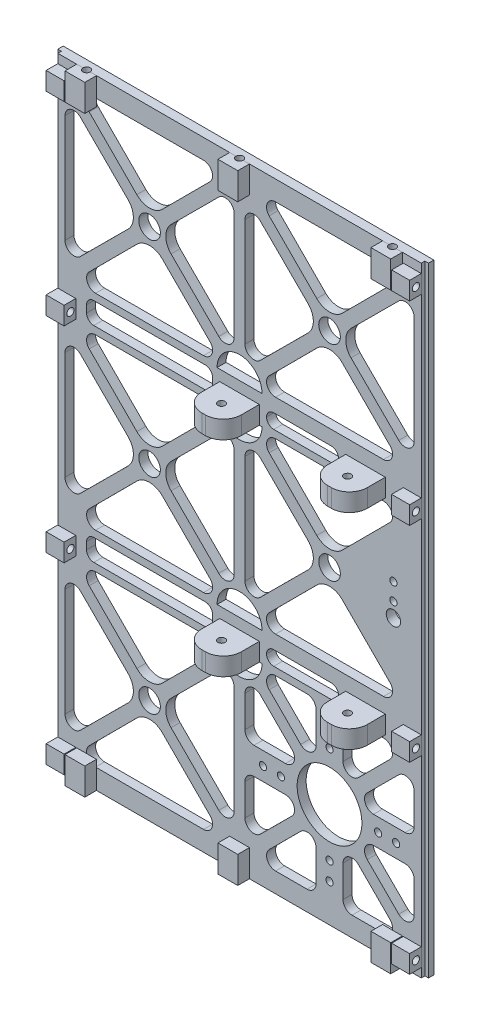
SolidWorks part; units mm, degrees
ref_plane "Přední rovina" through (0, 0, 0) normal (0, 0, 1) x (1, 0, 0)
ref_plane "Horní rovina" through (0, 0, 0) normal (0, 1, 0) x (1, 0, 0)
ref_plane "Pravá rovina" through (0, 0, 0) normal (1, 0, 0) x (0, 0, -1)
sketch "Skica1" plane through (0, 0, 0) normal (0, 0, 1) x (1, 0, 0)
  line L0 (0, 0) -> (0, 172) construction
  line L1 (-103, 172) -> (103, 172)
  line L2 (103, 172) -> (103, -172)
  line L3 (0, 0) -> (103, 0) construction
  line L4 (-103, 172) -> (-103, -172)
  line L5 (-103, -172) -> (103, -172)
  point P9 (-103, 0)
  dimension "D1" = 344
  dimension "D2" = 206
extrude "Přidat vysunutím1" add sketch "Skica1" along normal blind 5
sketch "Skica3" plane through (0, 0, 5) normal (0, 0, 1) x (1, 0, 0)
  line L0 (0, 0) -> (50, 0) construction
  line L1 (0, 0) -> (0, 172) construction
  line L2 (103, 172) -> (-103, 172) construction
  line L3 (50, 0) -> (50, 42) construction
  line L4 (50, 42) -> (80, 42) construction
  line L5 (50, 0) -> (0, 50) construction
  line L6 (11.5308, 33.5403) -> (38.0616, 7.0805)
  line L7 (83.5403, 38.4692) -> (57.0805, 11.9384)
  line L8 (16.4597, 38.4692) -> (42.9195, 11.9384)
  line L9 (20, 47) -> (80, 47)
  line L10 (3, 30) -> (3, -30)
  line L11 (11.5308, -33.5403) -> (38.0616, -7.0805)
  line L12 (16.4597, -38.4692) -> (42.9195, -11.9384)
  line L13 (20, -47) -> (80, -47)
  line L14 (83.5403, -38.4692) -> (57.0805, -11.9384)
  line L15 (97, 30) -> (97, -30)
  line L16 (88.4692, -33.5403) -> (61.9384, -7.0805)
  line L17 (88.4692, 33.5403) -> (61.9384, 7.0805)
  line L18 (0, 57) -> (103, 57) construction
  line L19 (103, -172) -> (103, 172) construction
  line L20 (0, -57) -> (103, -57) construction
  line L21 (16.4597, -152.4692) -> (42.9195, -125.9384)
  line L22 (20, -161) -> (80, -161)
  line L23 (83.5403, -152.4692) -> (57.0805, -125.9384)
  line L24 (88.4692, -147.5403) -> (61.9384, -121.0805)
  line L25 (88.4692, -80.4597) -> (61.9384, -106.9195)
  line L26 (97, -144) -> (97, -84)
  line L27 (20, -67) -> (80, -67)
  line L28 (83.5403, -75.5308) -> (57.0805, -102.0616)
  line L29 (16.4597, -75.5308) -> (42.9195, -102.0616)
  line L30 (3, -144) -> (3, -84)
  line L31 (11.5308, -80.4597) -> (38.0616, -106.9195)
  line L32 (11.5308, -147.5403) -> (38.0616, -121.0805)
  line L34 (20, 161) -> (80, 161)
  line L35 (83.5403, 152.4692) -> (57.0805, 125.9384)
  line L36 (16.4597, 152.4692) -> (42.9195, 125.9384)
  line L37 (3, 84) -> (3, 144)
  line L38 (11.5308, 147.5403) -> (38.0616, 121.0805)
  line L39 (11.5308, 80.4597) -> (38.0616, 106.9195)
  line L40 (16.4597, 75.5308) -> (42.9195, 102.0616)
  line L41 (20, 67) -> (80, 67)
  line L42 (83.5403, 75.5308) -> (57.0805, 102.0616)
  line L43 (88.4692, 80.4597) -> (61.9384, 106.9195)
  line L44 (88.4692, 147.5403) -> (61.9384, 121.0805)
  line L45 (97, 84) -> (97, 144)
  line L46 (-20, -161) -> (-80, -161)
  line L47 (-83.5403, -152.4692) -> (-57.0805, -125.9384)
  line L48 (-16.4597, -152.4692) -> (-42.9195, -125.9384)
  line L49 (-97, -144) -> (-97, -84)
  line L50 (-88.4692, -80.4597) -> (-61.9384, -106.9195)
  line L51 (-88.4692, -147.5403) -> (-61.9384, -121.0805)
  line L52 (-16.4597, -75.5308) -> (-42.9195, -102.0616)
  line L53 (-83.5403, -75.5308) -> (-57.0805, -102.0616)
  line L54 (-20, -67) -> (-80, -67)
  line L55 (-11.5308, -147.5403) -> (-38.0616, -121.0805)
  line L56 (-11.5308, -80.4597) -> (-38.0616, -106.9195)
  line L57 (-3, -144) -> (-3, -84)
  line L58 (-20, -47) -> (-80, -47)
  line L59 (-83.5403, -38.4692) -> (-57.0805, -11.9384)
  line L60 (-16.4597, -38.4692) -> (-42.9195, -11.9384)
  line L61 (-88.4692, 33.5403) -> (-61.9384, 7.0805)
  line L62 (-88.4692, -33.5403) -> (-61.9384, -7.0805)
  line L63 (-97, 30) -> (-97, -30)
  line L64 (-3, 30) -> (-3, -30)
  line L65 (-11.5308, -33.5403) -> (-38.0616, -7.0805)
  line L66 (-11.5308, 33.5403) -> (-38.0616, 7.0805)
  line L67 (-16.4597, 38.4692) -> (-42.9195, 11.9384)
  line L68 (-20, 47) -> (-80, 47)
  line L69 (-83.5403, 38.4692) -> (-57.0805, 11.9384)
  line L70 (-20, 67) -> (-80, 67)
  line L71 (-83.5403, 75.5308) -> (-57.0805, 102.0616)
  line L72 (-16.4597, 75.5308) -> (-42.9195, 102.0616)
  line L73 (-97, 84) -> (-97, 144)
  line L74 (-88.4692, 147.5403) -> (-61.9384, 121.0805)
  line L75 (-88.4692, 80.4597) -> (-61.9384, 106.9195)
  line L76 (-16.4597, 152.4692) -> (-42.9195, 125.9384)
  line L77 (-83.5403, 152.4692) -> (-57.0805, 125.9384)
  line L78 (-20, 161) -> (-80, 161)
  line L79 (-11.5308, 80.4597) -> (-38.0616, 106.9195)
  line L80 (-11.5308, 147.5403) -> (-38.0616, 121.0805)
  line L81 (-3, 84) -> (-3, 144)
  circle A0 centre (50, 0) radius 6
  arc A1 (83.5403, 38.4692) -> (80, 47) centre (80, 42) ccw
  arc A2 (42.9195, 11.9384) -> (57.0805, 11.9384) centre (50, 19) ccw
  arc A3 (16.4597, 38.4692) -> (20, 47) centre (20, 42) cw
  arc A4 (11.5308, 33.5403) -> (3, 30) centre (8, 30) ccw
  arc A5 (11.5308, -33.5403) -> (3, -30) centre (8, -30) cw
  arc A6 (38.0616, 7.0805) -> (38.0616, -7.0805) centre (31, 0) cw
  arc A7 (16.4597, -38.4692) -> (20, -47) centre (20, -42) ccw
  arc A8 (83.5403, -38.4692) -> (80, -47) centre (80, -42) cw
  arc A9 (42.9195, -11.9384) -> (57.0805, -11.9384) centre (50, -19) cw
  arc A10 (88.4692, 33.5403) -> (97, 30) centre (92, 30) cw
  arc A11 (88.4692, -33.5403) -> (97, -30) centre (92, -30) ccw
  arc A12 (61.9384, 7.0805) -> (61.9384, -7.0805) centre (69, 0) ccw
  arc A13 (16.4597, -152.4692) -> (20, -161) centre (20, -156) ccw
  arc A14 (83.5403, -152.4692) -> (80, -161) centre (80, -156) cw
  arc A15 (42.9195, -125.9384) -> (57.0805, -125.9384) centre (50, -133) cw
  circle A16 centre (50, -114) radius 6
  arc A17 (61.9384, -121.0805) -> (61.9384, -106.9195) centre (69, -114) cw
  arc A18 (88.4692, -80.4597) -> (97, -84) centre (92, -84) cw
  arc A19 (88.4692, -147.5403) -> (97, -144) centre (92, -144) ccw
  arc A20 (16.4597, -75.5308) -> (20, -67) centre (20, -72) cw
  arc A21 (83.5403, -75.5308) -> (80, -67) centre (80, -72) ccw
  arc A22 (42.9195, -102.0616) -> (57.0805, -102.0616) centre (50, -95) ccw
  arc A23 (11.5308, -147.5403) -> (3, -144) centre (8, -144) cw
  arc A24 (11.5308, -80.4597) -> (3, -84) centre (8, -84) ccw
  arc A25 (38.0616, -121.0805) -> (38.0616, -106.9195) centre (31, -114) ccw
  circle A26 centre (50, 114) radius 6
  arc A27 (16.4597, 152.4692) -> (20, 161) centre (20, 156) cw
  arc A28 (83.5403, 152.4692) -> (80, 161) centre (80, 156) ccw
  arc A29 (42.9195, 125.9384) -> (57.0805, 125.9384) centre (50, 133) ccw
  arc A30 (11.5308, 80.4597) -> (3, 84) centre (8, 84) cw
  arc A31 (11.5308, 147.5403) -> (3, 144) centre (8, 144) ccw
  arc A32 (38.0616, 106.9195) -> (38.0616, 121.0805) centre (31, 114) ccw
  arc A33 (16.4597, 75.5308) -> (20, 67) centre (20, 72) ccw
  arc A34 (83.5403, 75.5308) -> (80, 67) centre (80, 72) cw
  arc A35 (42.9195, 102.0616) -> (57.0805, 102.0616) centre (50, 95) cw
  arc A36 (61.9384, 106.9195) -> (61.9384, 121.0805) centre (69, 114) cw
  arc A37 (88.4692, 147.5403) -> (97, 144) centre (92, 144) cw
  arc A38 (88.4692, 80.4597) -> (97, 84) centre (92, 84) ccw
  arc A39 (-16.4597, -152.4692) -> (-20, -161) centre (-20, -156) cw
  arc A40 (-83.5403, -152.4692) -> (-80, -161) centre (-80, -156) ccw
  arc A41 (-42.9195, -125.9384) -> (-57.0805, -125.9384) centre (-50, -133) ccw
  arc A42 (-88.4692, -147.5403) -> (-97, -144) centre (-92, -144) cw
  arc A43 (-88.4692, -80.4597) -> (-97, -84) centre (-92, -84) ccw
  arc A44 (-61.9384, -121.0805) -> (-61.9384, -106.9195) centre (-69, -114) ccw
  circle A45 centre (-50, -114) radius 6
  arc A46 (-42.9195, -102.0616) -> (-57.0805, -102.0616) centre (-50, -95) cw
  arc A47 (-83.5403, -75.5308) -> (-80, -67) centre (-80, -72) cw
  arc A48 (-16.4597, -75.5308) -> (-20, -67) centre (-20, -72) ccw
  arc A49 (-38.0616, -121.0805) -> (-38.0616, -106.9195) centre (-31, -114) cw
  arc A50 (-11.5308, -80.4597) -> (-3, -84) centre (-8, -84) cw
  arc A51 (-11.5308, -147.5403) -> (-3, -144) centre (-8, -144) ccw
  arc A52 (-16.4597, -38.4692) -> (-20, -47) centre (-20, -42) cw
  arc A53 (-83.5403, -38.4692) -> (-80, -47) centre (-80, -42) ccw
  arc A54 (-42.9195, -11.9384) -> (-57.0805, -11.9384) centre (-50, -19) ccw
  arc A55 (-61.9384, 7.0805) -> (-61.9384, -7.0805) centre (-69, 0) cw
  arc A56 (-88.4692, -33.5403) -> (-97, -30) centre (-92, -30) cw
  arc A57 (-88.4692, 33.5403) -> (-97, 30) centre (-92, 30) ccw
  circle A58 centre (-50, 0) radius 6
  circle A59 centre (-50, 114) radius 6
  arc A60 (-11.5308, 33.5403) -> (-3, 30) centre (-8, 30) cw
  arc A61 (-11.5308, -33.5403) -> (-3, -30) centre (-8, -30) ccw
  arc A62 (-38.0616, 7.0805) -> (-38.0616, -7.0805) centre (-31, 0) ccw
  arc A63 (-16.4597, 38.4692) -> (-20, 47) centre (-20, 42) ccw
  arc A64 (-83.5403, 38.4692) -> (-80, 47) centre (-80, 42) cw
  arc A65 (-42.9195, 11.9384) -> (-57.0805, 11.9384) centre (-50, 19) cw
  arc A66 (-16.4597, 75.5308) -> (-20, 67) centre (-20, 72) cw
  arc A67 (-83.5403, 75.5308) -> (-80, 67) centre (-80, 72) ccw
  arc A68 (-42.9195, 102.0616) -> (-57.0805, 102.0616) centre (-50, 95) ccw
  arc A69 (-88.4692, 80.4597) -> (-97, 84) centre (-92, 84) cw
  arc A70 (-88.4692, 147.5403) -> (-97, 144) centre (-92, 144) ccw
  arc A71 (-61.9384, 106.9195) -> (-61.9384, 121.0805) centre (-69, 114) ccw
  arc A72 (-42.9195, 125.9384) -> (-57.0805, 125.9384) centre (-50, 133) cw
  arc A73 (-83.5403, 152.4692) -> (-80, 161) centre (-80, 156) cw
  arc A74 (-16.4597, 152.4692) -> (-20, 161) centre (-20, 156) ccw
  arc A75 (-38.0616, 106.9195) -> (-38.0616, 121.0805) centre (-31, 114) cw
  arc A76 (-11.5308, 147.5403) -> (-3, 144) centre (-8, 144) cw
  arc A77 (-11.5308, 80.4597) -> (-3, 84) centre (-8, 84) ccw
  dimension "12" = 12
  dimension "D3" = 60
  dimension "D4" = 10
  dimension "D5" = 20
  dimension "D8" = 45
  dimension "D2" = 50
  dimension "D6" = 23
  dimension "D7" = 42
  dimension "D9" = 57
extrude "Odebrat vysunutím2" cut sketch "Skica3" against normal blind 10
sketch "Skica21" plane through (0, 172, 0) normal (0, 1, 0) x (1, 0, 0)
  line L0 (103, -3) -> (101, -3)
  line L1 (103, -5) -> (103, 0) construction
  line L2 (101, -3) -> (101, -5)
  line L3 (103, -5) -> (-103, -5) construction
  line L4 (101, -5) -> (103, -5)
  line L5 (103, -5) -> (103, -3)
  line L6 (0, 0) -> (0, -5) construction
  line L7 (-103, -5) -> (-103, -3)
  line L8 (-101, -5) -> (-103, -5)
  line L9 (-101, -3) -> (-101, -5)
  line L10 (-103, -3) -> (-101, -3)
  dimension "D1" = 2
  dimension "D2" = 2
extrude "Odebrat vysunutím11" cut sketch "Skica21" against normal through all
sketch "Skica16" plane through (101, 0, 0) normal (1, 0, 0) x (0, 0, -1)
  line L0 (0, 0) -> (-52.2699, 0) construction
  line L1 (-5, -65) -> (-5, -55)
  line L2 (0, 162) -> (-37.7461, 162) construction
  line L4 (-5, -55) -> (-11.5, -55)
  line L20 (-11.5, -55) -> (-11.5, -65)
  line L21 (0, -172) -> (0, 172) construction
  line L22 (-5, 167) -> (-11.5, 167)
  line L23 (-5, -172) -> (-5, 172) construction
  line L24 (-11.5, 167) -> (-11.5, 157)
  line L25 (-5, 157) -> (-5, 167)
  line L26 (-5, 157) -> (-11.5, 157)
  line L27 (-5, 49) -> (-5, 59)
  line L28 (-5, 59) -> (-11.5, 59)
  line L29 (-11.5, 59) -> (-11.5, 49)
  line L30 (-5, 49) -> (-11.5, 49)
  line L35 (-5, -167) -> (-5, -157)
  line L36 (-5, -157) -> (-11.5, -157)
  line L37 (-11.5, -157) -> (-11.5, -167)
  line L38 (-5, -167) -> (-11.5, -167)
  line L39 (-5, -59) -> (-5, -49) [skipped]
  line L40 (-5, -49) -> (-11.5, -49) [skipped]
  line L41 (-11.5, -49) -> (-11.5, -59) [skipped]
  line L42 (-5, -59) -> (-11.5, -59) [skipped]
  line L43 (-5, -65) -> (-11.5, -65)
  point P14 (-5, 162)
  point P15 (-11.5, 162)
  dimension "D1" = 162
  dimension "D2" = 6.5
  dimension "D3" = 10
  dimension "D4" = 4
  dimension "D5" = 98
  dimension "D6" = 2
  dimension "D7" = 104
extrude "Přidat vysunutím5" add sketch "Skica16" against normal blind 10 separate body
pattern_linear "LinPole2" count 2 spacing 192 along (-1, 0, 0) of "Přidat vysunutím5"
sketch "Skica5" plane through (0, 0, 5) normal (0, 0, 1) x (1, 0, 0)
  line L0 (0, 0) -> (0, 59) construction
  line L17 (0, 59) -> (91, 59)
  line L18 (91, 49) -> (91, 59) construction
  line L21 (91, 59) -> (91, 49)
  line L22 (91, 49) -> (101, 49) construction
  line L23 (91, 49) -> (0, 49)
  line L28 (0, 49) -> (-11, 49)
  line L29 (-11, 49) -> (-11, 59)
  line L30 (-11, 59) -> (0, 59)
  line L31 (-101, 59) -> (-101, 49) construction
  point P14 (-101, 54)
  dimension "D1" = 90
extrude "Přidat vysunutím2" add sketch "Skica5" along normal blind 20
sketch "Skica19" plane through (101, 0, 0) normal (1, 0, 0) x (0, 0, -1)
  line L0 (-11.5, 162) -> (-8, 162) construction
  line L2 (-11.5, 167) -> (-11.5, 157) construction
  circle A0 centre (-8, 162) radius 2
  circle A4 centre (-8, 54) radius 2
  circle A6 centre (-8, -162) radius 2
  circle A7 centre (-8, -54) radius 2 [skipped]
  circle A8 centre (-8, -60) radius 2
  dimension "D2" = 4
  dimension "D3" = 4
  dimension "D4" = 108
  dimension "D5" = 4
  dimension "D7" = 114
  dimension "D1" = 3.5
  dimension "D6" = 2
extrude "Odebrat vysunutím10" cut sketch "Skica19" against normal through all
sketch "Skica8" plane through (0, 0, 5) normal (0, 0, 1) x (1, 0, 0)
  line L0 (0, 0) -> (50, 0) construction
  line L2 (92, 30) -> (92, -30) construction
  line L3 (50, 0) -> (69, 0) construction
  line L4 (61.9384, -7.0805) -> (88.4692, -33.5403)
  line L18 (61.9384, 7.0805) -> (88.4692, 33.5403)
  line L22 (97, -30) -> (97, 30)
  arc A13 (97, 30) -> (88.4692, 33.5403) centre (92, 30) ccw
  arc A14 (61.9384, 7.0805) -> (61.9384, -7.0805) centre (69, 0) ccw
  arc A17 (97, -30) -> (88.4692, -33.5403) centre (92, -30) cw
  dimension "D1" = 19
  dimension "D4" = 10
  dimension "D3" = 20
  dimension "D2" = 42
extrude "Přidat vysunutím3" add sketch "Skica8" against normal blind 5
sketch "Skica9" plane through (0, 0, 0) normal (0, 0, -1) x (-1, 0, 0)
  line L0 (-103, 0) -> (-85.5, 0) construction
  line L1 (-103, -172) -> (-103, 172) construction
  line L2 (-85.5, 0) -> (-85.5, -6.5) construction
  line L3 (-85.5, 0) -> (-85.5, 1.5) construction
  line L4 (-85.5, 0) -> (-85.5, 11) construction
  circle A0 centre (-85.5, -6.5) radius 4
  circle A1 centre (-85.5, 1.5) radius 2
  circle A2 centre (-85.5, 11) radius 2
  dimension "D3" = 8
  dimension "D5" = 4
  dimension "D7" = 4
  dimension "D1" = 17.5
  dimension "D2" = 6.5
  dimension "D4" = 1.5
  dimension "D6" = 11
extrude "Odebrat vysunutím6" cut sketch "Skica9" against normal through all
sketch "Skica11" plane through (0, 0, 0) normal (0, 0, -1) x (-1, 0, 0)
  circle A0 centre (-85.5, 11) radius 3
  circle A1 centre (-85.5, 1.5) radius 3
  dimension "D1" = 6
  dimension "D2" = 6
extrude "Odebrat vysunutím7" cut sketch "Skica11" against normal blind 2
pattern_linear "LinPole3" count 2 spacing 114 along (0, -1, 0) of "Přidat vysunutím2"
sketch "Skica12" plane through (0, 0, 5) normal (0, 0, 1) x (1, 0, 0)
  line L0 (97, -114) -> (50, -114) construction
  line L6 (50, -114) -> (50, -67) construction
  line L7 (80, -67) -> (20, -67) construction
  line L12 (97, -144) -> (97, -84) construction
  line L13 (97, -121.5) -> (97, -106.5)
  line L14 (97, -106.5) -> (59, -106.5)
  line L15 (59, -106.5) -> (59, -121.5)
  line L16 (97, -121.5) -> (59, -121.5)
  line L17 (82, -114) -> (82, -106.5) construction
  line L18 (3, -121.5) -> (3, -106.5)
  line L19 (3, -106.5) -> (41, -106.5)
  line L20 (41, -106.5) -> (41, -121.5)
  line L21 (3, -121.5) -> (41, -121.5)
  line L32 (50, -114) -> (13.569, -77.569) construction
  line L33 (57.5, -161) -> (42.5, -161)
  line L34 (42.5, -161) -> (42.5, -123)
  line L35 (42.5, -123) -> (57.5, -123)
  line L36 (57.5, -161) -> (57.5, -123)
  line L37 (57.5, -67) -> (42.5, -67)
  line L38 (57.5, -67) -> (57.5, -105)
  line L39 (42.5, -105) -> (57.5, -105)
  line L40 (42.5, -67) -> (42.5, -105)
  circle A0 centre (87, -114) radius 2
  circle A8 centre (77, -114) radius 2
  circle A9 centre (13, -114) radius 2
  circle A10 centre (23, -114) radius 2
  circle A11 centre (50, -141) radius 2
  circle A12 centre (50, -151) radius 2
  circle A13 centre (50, -87) radius 2
  circle A14 centre (50, -77) radius 2
  point P7 (59, -114)
  dimension "D4" = 4
  dimension "D5" = 10
  dimension "D6" = 45
  dimension "D1" = 38
  dimension "D2" = 15
  dimension "D3" = 23
extrude "Přidat vysunutím4" add sketch "Skica12" against normal blind 5
sketch "Skica6" plane through (0, 59, 0) normal (0, 1, 0) x (1, 0, 0)
  line L0 (0, 0) -> (0, -15) construction
  line L1 (103, 0) -> (-103, 0) construction
  line L2 (0, -15) -> (70, -15) construction
  line L3 (101, -5) -> (-101, -5) construction
  circle A0 centre (70, -15) radius 2
  circle A3 centre (0, -15) radius 2
  circle A4 centre (45, -15) radius 6
  dimension "D3" = 4
  dimension "D4" = 70
  dimension "D2" = 2
  dimension "D6" = 25
  dimension "D7" = 12
  dimension "D1" = 10
  dimension "D5" = 70
extrude "Odebrat vysunutím8" cut sketch "Skica6" against normal through all
fillet "Zaoblit1" radius 5 16 edges at (37.641, -121.5, 2.5) (3, -121.5, 2.5) (37.641, -106.5, 2.5) (3, -106.5, 2.5) (97, -121.5, 2.5) (62.359, -121.5, 2.5) (62.359, -106.5, 2.5) (97, -106.5, 2.5) (42.5, -161, 2.5) (57.5, -161, 2.5) (57.5, -126.359, 2.5) (42.5, -126.359, 2.5) (57.5, -67, 2.5) (57.5, -101.641, 2.5) (42.5, -67, 2.5) (42.5, -101.641, 2.5)
sketch "Skica22" plane through (101, 0, 0) normal (1, 0, 0) x (0, 0, -1)
  line L0 (-11.5, -162) -> (-8, -162) construction
  line L4 (-11.5, -157) -> (-11.5, -167) construction
  line L5 (0, -172) -> (0, 172) construction
  circle A1 centre (-8, -162) radius 2
  dimension "D2" = 4
  dimension "D1" = 8
extrude "Odebrat vysunutím12" cut sketch "Skica22" against normal through all
sketch "Skica23" plane through (0, 0, 5) normal (0, 0, 1) x (1, 0, 0)
  line L0 (0, 172) -> (0, 63.4853) construction
  line L1 (101, 172) -> (-101, 172) construction
  line L2 (85, 172) -> (85, 142.9236) construction
  line L3 (85, 172) -> (90.5, 172)
  line L4 (90.5, 172) -> (90.5, 157)
  line L5 (90.5, 157) -> (79.5, 157)
  line L6 (79.5, 172) -> (79.5, 157)
  line L7 (85, 172) -> (79.5, 172)
  line L8 (0, 172) -> (-5.5, 172)
  line L9 (-5.5, 172) -> (-5.5, 157)
  line L10 (5.5, 157) -> (-5.5, 157)
  line L11 (5.5, 172) -> (5.5, 157)
  line L12 (0, 172) -> (5.5, 172)
  line L13 (-85, 172) -> (-90.5, 172)
  line L14 (-90.5, 172) -> (-90.5, 157)
  line L15 (-79.5, 157) -> (-90.5, 157)
  line L16 (-79.5, 172) -> (-79.5, 157)
  line L17 (-85, 172) -> (-79.5, 172)
  point P9 (87.75, 172)
  point P12 (85, 157)
  point P13 (82.25, 172)
  dimension "D1" = 85
  dimension "D2" = 15
  dimension "D3" = 11
  dimension "D4" = 3
  dimension "D5" = 85
extrude "Přidat vysunutím9" add sketch "Skica23" along normal blind 6.5 separate body
sketch "Skica24" plane through (0, 172, 0) normal (0, 1, 0) x (1, 0, 0)
  line L0 (-85, 0) -> (-85, -5) construction
  line L1 (103, 0) -> (-103, 0) construction
  circle A1 centre (-85, -5) radius 2
  circle A2 centre (0, -5) radius 2
  circle A3 centre (85, -5) radius 2
  dimension "D1" = 85
  dimension "D3" = 4
  dimension "D4" = 3
  dimension "D2" = 5
  dimension "D5" = 85
extrude "Odebrat vysunutím13" cut sketch "Skica24" against normal blind 12
sketch "Skica25" plane through (0, 59, 0) normal (0, 1, 0) x (1, 0, 0)
  line L0 (0, -15) -> (0, -5) construction
  line L1 (91, -5) -> (-11, -5) construction
  line L2 (-11, -5) -> (-11, -25) construction
  line L3 (-11, -25) -> (-11, -5) construction
  line L4 (91, -25) -> (-11, -25) construction
  line L5 (11, -5) -> (11, -25)
  line L6 (11, -25) -> (59, -25)
  line L7 (59, -25) -> (59, -5)
  line L8 (59, -5) -> (11, -5)
  line L10 (91, -5) -> (81, -5)
  line L11 (91, -5) -> (91, -25)
  line L12 (91, -25) -> (81, -25)
  line L13 (81, -5) -> (81, -25)
  circle A0 centre (70, -15) radius 2 construction
  dimension "D1" = 11
  dimension "D2" = 11
extrude "Odebrat vysunutím14" cut sketch "Skica25" against normal blind 130
pattern_linear "LinPole4" count 2 spacing 329 along (0, -1, 0) of "Přidat vysunutím9"
mirror "Zrcadlit4" about plane through (0, 0, 0) normal (0, 1, 0) of "Odebrat vysunutím13"
fillet "Zaoblit2" radius 10 8 edges at (-11, -60, 25) (11, -60, 25) (59, -60, 25) (81, -60, 25) (81, 54, 25) (59, 54, 25) (11, 54, 25) (-11, 54, 25)
sketch "Skica26" plane through (0, 0, 5) normal (0, 0, 1) x (1, 0, 0)
  line L0 (-85, -42) -> (-85, -51) construction
  line L2 (-85, -51) -> (-85, -63)
  line L5 (-50, 0) -> (-50, -47) construction
  line L6 (-80, -47) -> (-20, -47) construction
  line L7 (-85, -51) -> (-15, -51)
  line L8 (-85, -63) -> (-15, -63)
  line L9 (-50, -63) -> (-50, -47) construction
  line L10 (0, 157) -> (0, 65) construction
  line L11 (-15, -51) -> (-15, -63)
  line L12 (-50, 0) -> (-91.8146, 0) construction
  line L13 (-85, 51) -> (-85, 63)
  line L14 (-85, 63) -> (-15, 63)
  line L15 (-15, 51) -> (-15, 63)
  line L16 (-85, 51) -> (-15, 51)
  line L17 (-5.5, 157) -> (5.5, 157) construction
  line L18 (-15, 57) -> (26.408, 57) construction
  line L19 (12.5, 65) -> (0, 65) construction
  line L20 (12.5, 65) -> (-12.5, 65)
  line L21 (12.5, 49) -> (-12.5, 49)
  line L22 (12.5, -65) -> (-12.5, -65)
  line L23 (12.5, -49) -> (-12.5, -49)
  line L24 (15, -55) -> (15, -63)
  line L25 (15, 59) -> (55, 59)
  line L26 (15, 59) -> (15, 51)
  line L27 (15, 51) -> (55, 51)
  line L28 (55, 59) -> (55, 51)
  line L29 (11, 59) -> (-11, 59) construction
  line L30 (11, 49) -> (11, 59) construction
  line L31 (59, 49) -> (59, 59) construction
  line L32 (15, -55) -> (55, -55)
  line L33 (55, -55) -> (55, -63)
  line L34 (15, -63) -> (55, -63)
  circle A0 centre (50, -114) radius 18
  arc A2 (12.5, 65) -> (-12.5, 65) centre (0, 65) ccw
  arc A3 (-83.5403, -38.4692) -> (-80, -47) centre (-80, -42) ccw construction
  arc A4 (12.5, 49) -> (-12.5, 49) centre (0, 49) cw
  arc A5 (12.5, -65) -> (-12.5, -65) centre (0, -65) cw
  arc A6 (12.5, -49) -> (-12.5, -49) centre (0, -49) ccw
  point P17 (-50, -51)
  dimension "D1" = 36
  dimension "D2" = 12
  dimension "D4" = 25
  dimension "D5" = 2
  dimension "D7" = 8
  dimension "D8" = 4
  dimension "D6" = 114
  dimension "D3" = 63
  dimension "D9" = 4
  dimension "D11" = 114
  dimension "D10" = 2
extrude "Odebrat vysunutím15" cut sketch "Skica26" against normal through all
fillet "Zaoblit3" radius 4 16 edges at (-15, 51, 2.5) (-15, 63, 2.5) (-85, 63, 2.5) (-85, 51, 2.5) (-85, -63, 2.5) (-85, -51, 2.5) (-15, -63, 2.5) (-15, -51, 2.5) (55, 59, 2.5) (55, 51, 2.5) (15, 59, 2.5) (15, 51, 2.5) (55, -55, 2.5) (55, -63, 2.5) (15, -55, 2.5) (15, -63, 2.5)
sketch "Skica28" plane through (101, 0, 0) normal (1, 0, 0) x (0, 0, -1)
  line L0 (-11.5, -60) -> (-8, -60) construction
  line L1 (-11.5, -55) -> (-11.5, -65) construction
  line L2 (-8, 54) -> (-8, -60) construction
  circle A0 centre (-8, -60) radius 2
  dimension "D1" = 4
extrude "Odebrat vysunutím16" cut sketch "Skica28" against normal blind 10
pattern_linear "LinPole5" count 2 spacing 192 along (-1, 0, 0) of "Odebrat vysunutím16"
